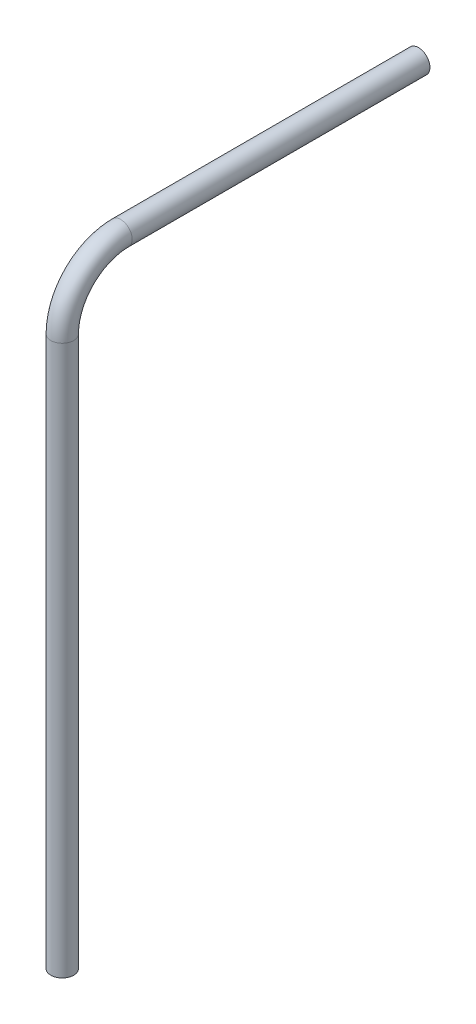
SolidWorks part; units mm, degrees
material "Cast Carbon Steel"
ref_plane "Front Plane" through (0, 0, 0) normal (0, 0, 1) x (1, 0, 0)
ref_plane "Top Plane" through (0, 0, 0) normal (0, 1, 0) x (1, 0, 0)
ref_plane "Right Plane" through (0, 0, 0) normal (1, 0, 0) x (0, 0, -1)
sketch "Sketch2" plane through (0, 0, 0) normal (1, 0, 0) x (0, 0, -1)
  arc A0 (-64.8338, 0) -> (0, 64.8338) centre (0, 0) cw
  dimension "D1" = 64.8338
sketch "Sketch3" plane through (0, 0, 0) normal (0, 1, 0) x (1, 0, 0)
  circle A0 centre (0, -64.8338) radius 12.7
  circle A1 centre (0, -64.8338) radius 4.7625
  dimension "D1" = 25.4
  dimension "D2" = 7.9375
sweep "Sweep1" add profiles "Sketch3" path "Sketch2"
ref_plane "Plane1" through (0, 0, 0) normal (0, -1, 0) x (-1, 0, 0)
ref_plane "Plane2" through (0, 0, 0) normal (0, 0, -1) x (-1, 0, 0)
sketch "Sketch4" plane through (0, 0, 0) normal (0, -1, 0) x (-1, 0, 0)
  circle A0 centre (0, -64.8338) radius 12.7
  circle A1 centre (0, -64.8338) radius 4.7625
  dimension "D1" = 7.9375
  dimension "D2" = 25.4
  dimension "D3" = 64.8338
extrude "Boss-Extrude3" add sketch "Sketch4" along normal blind 609.6
sketch "Sketch5" plane through (0, 0, 0) normal (0, 0, -1) x (-1, 0, 0)
  circle A2 centre (0, 64.8338) radius 4.7625
  circle A3 centre (0, 64.8338) radius 12.7
  circle A5 centre (0, 64.8338) radius 12.7 construction
  dimension "D1" = 9.525
  dimension "D2" = 25.4
extrude "Boss-Extrude4" add sketch "Sketch5" along normal blind 330.2
ref_plane "Plane3" through (-12.7, 0, 0) normal (-1, 0, 0) x (0, 0, 1)
sketch "Sketch6" plane through (-12.7, 0, 0) normal (-1, 0, 0) x (0, 0, 1)
  line L0 (52.1338, 0) -> (77.5338, 0) construction
  line L1 (57.15, -609.6) -> (69.85, -609.6)
  line L2 (57.15, -609.6) -> (57.15, 0)
  line L3 (57.15, 0) -> (69.85, 0)
  line L4 (69.85, -609.6) -> (69.85, 0)
  point P12 (63.5, -609.6)
  point P13 (63.5, -609.6)
  dimension "D1" = 57.15
  dimension "D2" = 63.5
  dimension "D3" = 609.6
extrude "Cut-Extrude1" cut sketch "Sketch6" against normal blind 6.35
